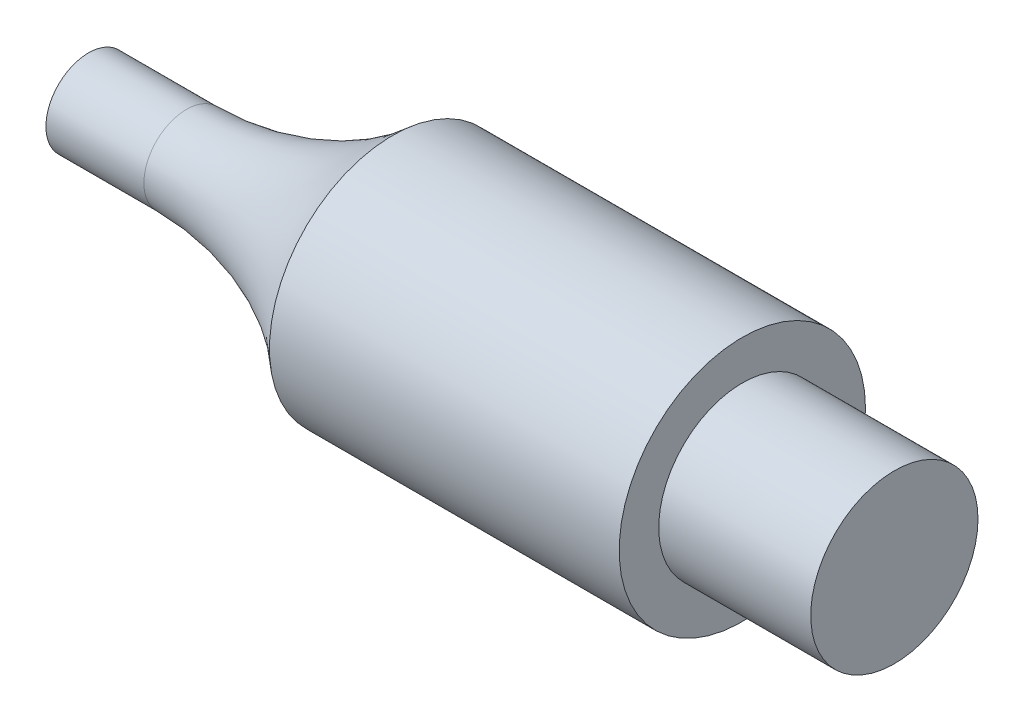
SolidWorks part; units mm, degrees
ref_plane "前视基准面" through (0, 0, 0) normal (0, 0, 1) x (1, 0, 0)
ref_plane "上视基准面" through (0, 0, 0) normal (0, 1, 0) x (1, 0, 0)
ref_plane "右视基准面" through (0, 0, 0) normal (1, 0, 0) x (0, 0, -1)
sketch "草图1" plane through (0, 0, 0) normal (0, 1, 0) x (1, 0, 0)
  line L0 (-10.4424, -1.725) -> (-59.3317, -1.725) construction
  line L1 (-26.9424, 2.325) -> (-15.4424, 2.325)
  line L2 (-26.9424, 2.325) -> (-26.9424, -5.775)
  line L3 (-26.9424, -5.775) -> (-15.4424, -5.775)
  line L4 (-15.4424, 2.325) -> (-15.4424, -5.775)
  line L5 (-15.4424, 1.025) -> (-10.4424, 1.025)
  line L6 (-15.4424, 1.025) -> (-15.4424, -4.475)
  line L7 (-15.4424, -4.475) -> (-10.4424, -4.475)
  line L8 (-10.4424, 1.025) -> (-10.4424, -4.475)
  line L10 (-26.9424, -0.3236) -> (-36.9424, -0.3236)
  line L11 (-26.9424, -0.3236) -> (-26.9424, -3.1264)
  line L12 (-26.9424, -3.1264) -> (-36.9424, -3.1264)
  line L13 (-36.9424, -0.3236) -> (-36.9424, -3.1264)
  point P8 (-10.4424, -1.725)
  point P9 (-26.9424, -1.725)
  point P16 (-36.9424, -1.725)
  dimension "D1" = 5.5
  dimension "D2" = 5
  dimension "D3" = 8.1
  dimension "D4" = 16.5
  dimension "D5" = 10
revolve "旋转1" add sketch "草图1" angle 360 about L0 region at (-12.9424, 0, 0.35) region at (-21.1924, 0, -0.3)
revolve "旋转2" add sketch "草图1<3>" angle 360 about L0 region at (-31.9424, 0, 1.0243)
sketch "草图1<3>" plane through (0, 0, 0) normal (0, 1, 0) x (1, 0, 0) same geometry as "草图1"
fillet "圆角1" radius 10 1 edges at (-26.9424, 0, 0.3236)
